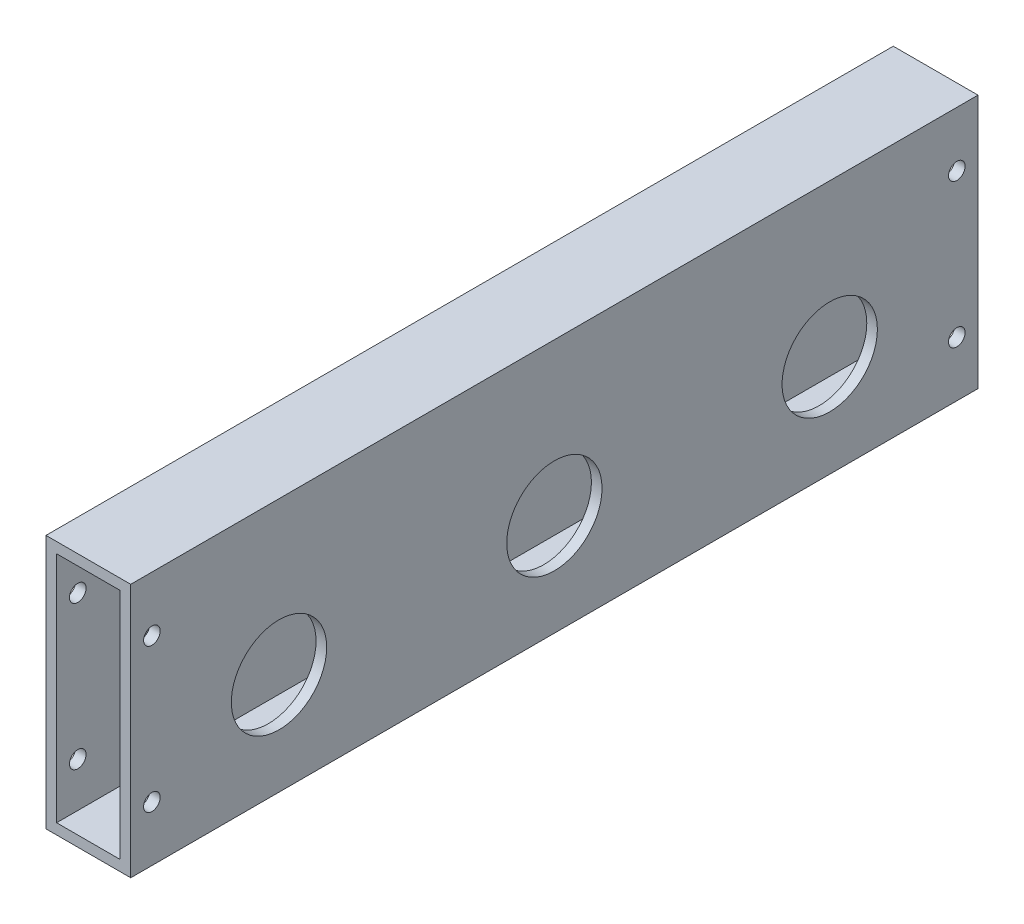
SolidWorks part; units mm, degrees
material "6061-T6 (SS)"
ref_plane "Front Plane" through (0, 0, 0) normal (0, 0, 1) x (1, 0, 0)
ref_plane "Top Plane" through (0, 0, 0) normal (0, 1, 0) x (1, 0, 0)
ref_plane "Right Plane" through (0, 0, 0) normal (1, 0, 0) x (0, 0, -1)
sketch "Sketch1" plane through (0, 0, 0) normal (1, 0, 0) x (0, 0, -1)
  line L1 (-127, 38.1) -> (127, 38.1)
  line L2 (-127, 38.1) -> (-127, -38.1)
  line L3 (-127, -38.1) -> (127, -38.1)
  line L4 (127, 38.1) -> (127, -38.1)
  line L5 (-127, 38.1) -> (127, -38.1) construction
  line L6 (-127, -38.1) -> (127, 38.1) construction
  point P0 (0, 0)
  dimension "D1" = 76.2
  dimension "D2" = 254
extrude "Boss-Extrude1" add sketch "Sketch1" along normal blind 25.4
shell "Shell1" thickness 3.175 removed face at (12.7, 0, -127) removed face at (12.7, 0, 127)
sketch "Sketch2" plane through (25.4, 0, 0) normal (1, 0, 0) x (0, 0, -1)
  line L0 (-127, -38.1) -> (127, -38.1) construction
  circle A0 centre (0, -7.62) radius 14.2875
  circle A1 centre (-82.55, -7.62) radius 14.2875
  circle A2 centre (82.55, -7.62) radius 14.2875
  circle A3 centre (-82.55, -7.62) radius 38.1 construction
  circle A4 centre (0, -7.62) radius 38.1 construction
  circle A5 centre (82.55, -7.62) radius 38.1 construction
  point P11 (0, 0)
  dimension "D1" = 28.575
  dimension "D5" = 76.2
  dimension "D2" = 30.48
  dimension "D3" = 82.55
  dimension "D4" = 82.55
  dimension "D6" = 0
extrude "Cut-Extrude1" cut sketch "Sketch2" against normal through all
sketch "Sketch3" plane through (25.4, 0, 0) normal (1, 0, 0) x (0, 0, -1)
  line L0 (-120.65, 21.59) -> (-120.65, -21.59) construction
  line L1 (-127, 38.1) -> (-127, -38.1) construction
  point P2 (-120.65, 0)
  point P3 (-127, 0)
  dimension "D1" = 43.18
  dimension "D2" = 6.35
hole_wizard "#10 Clearance Hole1" positions "Sketch4" profile "Sketch6" hole size "#10" standard "ANSI Inch" end condition through all
sketch "Sketch4" plane through (25.4, 0, 0) normal (1, 0, 0) x (0, 0, -1)
  point P0 (-120.65, 21.59)
  point P3 (-120.65, -21.59)
sketch "Sketch6" plane through (25.4, 21.59, 120.65) normal (0, 1, 0) x (0, 0, -1)
  line L0 (0, 0) -> (0, 25.4)
  line L1 (0, 25.4) -> (2.4892, 25.4)
  line L2 (2.4892, 25.4) -> (2.4892, 0)
  line L5 (2.4892, 0) -> (0, 0)
  line L11 (0, -6.35) -> (0, 107.95) construction
  dimension "Thru Hole Dia." = 4.9784
  dimension "Thru Hole Depth" = 25.4
mirror "Mirror1" about plane through (0, 0, 0) normal (0, 0, 1) of "#10 Clearance Hole1"
